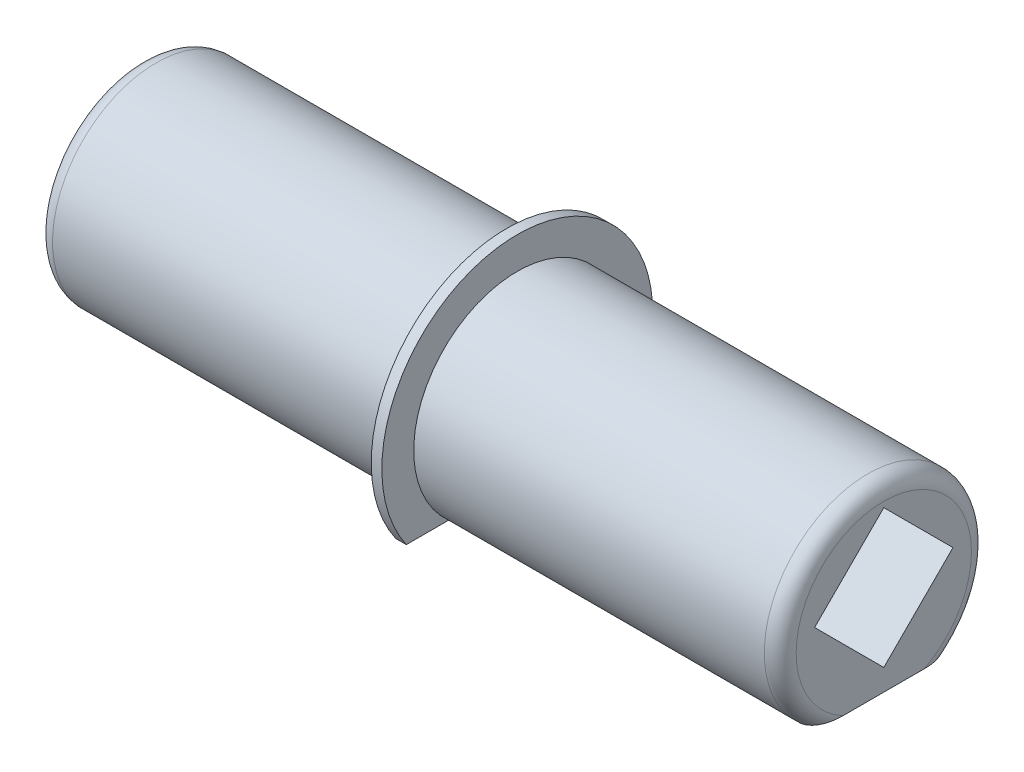
SolidWorks part; units mm, degrees
ref_plane "Plan de face" through (0, 0, 0) normal (0, 0, 1) x (1, 0, 0)
ref_plane "Plan de dessus" through (0, 0, 0) normal (0, 1, 0) x (1, 0, 0)
ref_plane "Plan de droite" through (0, 0, 0) normal (1, 0, 0) x (0, 0, -1)
sketch "Esquisse1" plane through (0, 0, 0) normal (1, 0, 0) x (0, 0, -1)
  line L0 (-6.4508, -7.3109) -> (6.4508, -7.3109)
  arc A0 (-6.4508, -7.3109) -> (6.4508, -7.3109) centre (0, 0) cw
  point P6 (0, -7.3109)
  dimension "D1" = 9.75
extrude "Boss.-Extru.1" add sketch "Esquisse1" along normal mid plane 70
sketch "Esquisse3" plane through (0, 0, 0) normal (1, 0, 0) x (0, 0, -1)
  line L0 (-10.4457, -7.3109) -> (10.4457, -7.3109)
  line L1 (-6.4508, -7.3109) -> (6.4508, -7.3109) construction
  arc A2 (8.4357, -9.5604) -> (-8.4357, -9.5604) centre (0, 0) ccw
  arc A3 (10.4457, -7.3109) -> (-10.4457, -7.3109) centre (0, 0) ccw
  dimension "D1" = 3
extrude "Boss.-Extru.2" add sketch "Esquisse3" along normal mid plane 1
sketch "Esquisse2" plane through (0, 0, 0) normal (1, 0, 0) x (0, 0, -1)
  line L0 (0, 9.75) -> (0, 7.733) construction
  line L7 (0, -5.2939) -> (0, -7.3109) construction
  line L8 (-6.4508, -7.3109) -> (6.4508, -7.3109) construction
  line L9 (-6.5134, 1.2195) -> (0, -5.2939)
  line L16 (-6.5134, 1.2195) -> (0, 7.733)
  line L17 (0, -5.2939) -> (6.5134, 1.2195)
  line L18 (0, 7.733) -> (6.5134, 1.2195)
  line L19 (-6.5134, 1.2195) -> (6.5134, 1.2195) construction
  line L20 (0, -5.2939) -> (0, 7.733) construction
  arc A1 (6.4508, -7.3109) -> (-6.4508, -7.3109) centre (0, 0) ccw construction
extrude "Enlèv. mat.-Extru.1" cut sketch "Esquisse2" against normal mid plane 100
fillet "Congé1" radius 1.5 2 edges at (-35, 9.75, 0) (35, 9.75, 0)
